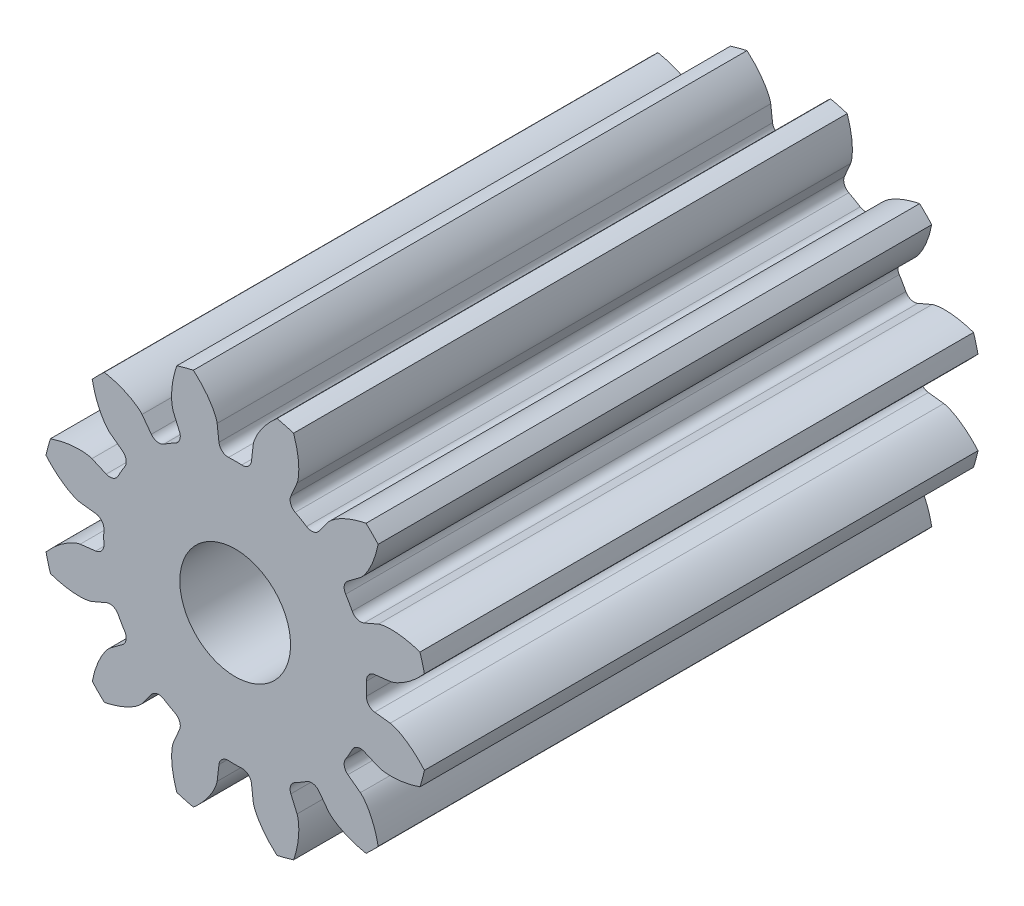
SolidWorks part; units mm, degrees
ref_plane "Front Plane" through (0, 0, 0) normal (0, 0, 1) x (1, 0, 0)
ref_plane "Top Plane" through (0, 0, 0) normal (0, 1, 0) x (1, 0, 0)
ref_plane "Right Plane" through (0, 0, 0) normal (1, 0, 0) x (0, 0, -1)
sketch "Sketch1" plane through (0, 0, 0) normal (0, 0, 1) x (1, 0, 0)
  line L0 (0, 0) -> (0, 4.7625) construction
  line L1 (-1.5306, 5.3196) -> (1.5306, 4.2054) construction
  circle A0 centre (0, 0) radius 3.7703 construction
  circle A1 centre (0, 0) radius 5.5562 construction
  circle A2 centre (0, 0) radius 4.7625 construction
  circle A3 centre (0, 0) radius 4.4753 construction
  point P8 (406.4, 0)
  point P13 (152.4, 0)
  dimension "OD | Outside Diameter" = 11.1125
  dimension "Root Diameter" = 7.5406
  dimension "Gear Pitch Diameter" = 9.525
  dimension "Base Diameter" = 8.9506
  dimension "Pressure Angle" = 20
  dimension "Number of Teeth" = 304.8
  dimension "Gear Pitch | Diametral Pitch" = 812.8
sketch "Sketch2" plane through (0, 0, 0) normal (1, 0, 0) x (0, 0, -1)
  line L0 (-152.4, 0) -> (152.4, 0) construction
  point P2 (-146.8438, 0)
  point P5 (-144.0656, 0)
  point P6 (146.8438, 0)
  dimension "Length" = 304.8
  dimension "D1" = 5.5562
  dimension "D2" = 8.3344
  dimension "D3" = 5.5562
sketch "Sketch3" plane through (0, 0, 0) normal (0, 0, 1) x (1, 0, 0)
  circle A0 centre (0, 0) radius 5.5562
  circle A1 centre (0, 0) radius 5.5562 construction
extrude "Boss-Extrude1" add sketch "Sketch3" against normal up to vertex (152.4 mm away) and the other way up to vertex (152.4 mm away) up to point (0, 0, -152.4) other way up to point (0, 0, 152.4)
sketch "Sketch4" plane through (0, 0, 0) normal (0, 0, 1) x (1, 0, 0)
  line L0 (0, 0) -> (3.745, 0.4364) construction
  line L2 (0, 0) -> (3.745, -0.4364) construction
  line L4 (3.745, 0.4364) -> (4.4452, 0.5179)
  line L5 (4.4452, -0.5179) -> (3.745, -0.4364)
  arc A0 (3.745, 0.4364) -> (3.745, -0.4364) centre (0, 0) cw
  arc A3 (5.4254, 1.1987) -> (5.4254, -1.1987) centre (0, 0) cw
  circle A4 centre (0, 0) radius 5.5562 construction
  spline S0 degree 4 poles (4.4452, 0.5179) (4.447, 0.5182) (4.452, 0.5189) (4.4613, 0.5207) (4.4765, 0.524) (4.4957, 0.5289) (4.5203, 0.5361) (4.5491, 0.5456) (4.5805, 0.5571) (4.6143, 0.5707) (4.6477, 0.5853) (4.6807, 0.6008) (4.7133, 0.6171) (4.7525, 0.6378) (4.799, 0.6639) (4.8525, 0.6964) (4.9122, 0.7355) (4.9721, 0.7778) (5.03, 0.8214) (5.0874, 0.8676) (5.1422, 0.9139) (5.1978, 0.9642) (5.2486, 1.0117) (5.304, 1.0674) (5.3484, 1.113) (5.4053, 1.1756) (5.4385, 1.2134) (5.4767, 1.2584) (5.4934, 1.2789) (5.5037, 1.2914) knots 0 0 0 0 0 0.005377 0.015084 0.028532 0.04661 0.064855 0.092111 0.119476 0.146842 0.174209 0.201575 0.228941 0.256307 0.307035 0.361767 0.4165 0.471232 0.525964 0.580697 0.635429 0.690161 0.744894 0.799626 0.854358 0.909091 0.954545 1 1 1 1 1 construction
  spline S1 degree 4 poles (4.4452, 0.5179) (4.447, 0.5182) (4.452, 0.5189) (4.4613, 0.5207) (4.4765, 0.524) (4.4957, 0.5289) (4.5203, 0.5361) (4.5491, 0.5456) (4.5805, 0.5571) (4.6143, 0.5707) (4.6477, 0.5853) (4.6807, 0.6008) (4.7133, 0.6171) (4.7525, 0.6378) (4.799, 0.6639) (4.8525, 0.6964) (4.9122, 0.7355) (4.9721, 0.7778) (5.03, 0.8214) (5.0874, 0.8676) (5.1422, 0.9139) (5.1978, 0.9642) (5.2486, 1.0117) (5.304, 1.0674) (5.3484, 1.113) (5.393, 1.1621) (5.4145, 1.1862) (5.4254, 1.1987) knots 0 0 0 0 0 0.005377 0.015084 0.028532 0.04661 0.064855 0.092111 0.119476 0.146842 0.174209 0.201575 0.228941 0.256307 0.307035 0.361767 0.4165 0.471232 0.525964 0.580697 0.635429 0.690161 0.744894 0.799626 0.854358 0.909091 0.909091 0.909091 0.909091 0.909091
  spline S2 degree 4 poles (4.4452, -0.5179) (4.447, -0.5182) (4.452, -0.5189) (4.4613, -0.5207) (4.4765, -0.524) (4.4957, -0.5289) (4.5203, -0.5361) (4.5491, -0.5456) (4.5805, -0.5571) (4.6143, -0.5707) (4.6477, -0.5853) (4.6807, -0.6008) (4.7133, -0.6171) (4.7525, -0.6378) (4.799, -0.6639) (4.8525, -0.6964) (4.9122, -0.7355) (4.9721, -0.7778) (5.03, -0.8214) (5.0874, -0.8676) (5.1422, -0.9139) (5.1978, -0.9642) (5.2486, -1.0117) (5.304, -1.0674) (5.3484, -1.113) (5.4053, -1.1756) (5.4385, -1.2134) (5.4767, -1.2584) (5.4934, -1.2789) (5.5037, -1.2914) knots 0 0 0 0 0 0.005377 0.015084 0.028532 0.04661 0.064855 0.092111 0.119476 0.146842 0.174209 0.201575 0.228941 0.256307 0.307035 0.361767 0.4165 0.471232 0.525964 0.580697 0.635429 0.690161 0.744894 0.799626 0.854358 0.909091 0.954545 1 1 1 1 1 construction
  spline S3 degree 4 poles (4.4452, -0.5179) (4.447, -0.5182) (4.452, -0.5189) (4.4613, -0.5207) (4.4765, -0.524) (4.4957, -0.5289) (4.5203, -0.5361) (4.5491, -0.5456) (4.5805, -0.5571) (4.6143, -0.5707) (4.6477, -0.5853) (4.6807, -0.6008) (4.7133, -0.6171) (4.7525, -0.6378) (4.799, -0.6639) (4.8525, -0.6964) (4.9122, -0.7355) (4.9721, -0.7778) (5.03, -0.8214) (5.0874, -0.8676) (5.1422, -0.9139) (5.1978, -0.9642) (5.2486, -1.0117) (5.304, -1.0674) (5.3484, -1.113) (5.393, -1.1621) (5.4145, -1.1862) (5.4254, -1.1987) knots 0 0 0 0 0 0.005377 0.015084 0.028532 0.04661 0.064855 0.092111 0.119476 0.146842 0.174209 0.201575 0.228941 0.256307 0.307035 0.361767 0.4165 0.471232 0.525964 0.580697 0.635429 0.690161 0.744894 0.799626 0.854358 0.909091 0.909091 0.909091 0.909091 0.909091
  dimension "D1" = 7.5406
extrude "Cut-Extrude1" cut sketch "Sketch4" against normal through all both and the other way through all
fillet "Fillet1" radius 0.2663 2 edges at (3.745, -0.4364, 0) (3.745, 0.4364, 0)
pattern_circular "CirPattern1" count 12 over 360 about axis through (0, 0, 152.4) along (0, 0, -1) of "Cut-Extrude1", "Fillet1"
sketch "Sketch6" plane through (0, 0, 152.4) normal (0, 0, 1) x (1, 0, 0)
  circle A0 centre (0, 0) radius 6.35
  dimension "D1" = 12.7
extrude "Cut-Extrude2" cut sketch "Sketch6" against normal blind 288.925
sketch "Sketch7" plane through (0, 0, -152.4) normal (0, 0, -1) x (-1, 0, 0)
  point P0 (0, 0)
hole_wizard "1/8 (0.125) Diameter Hole1" positions "Sketch7" profile "Sketch8" hole size "1/8" standard "ANSI Inch" end condition through all
sketch "Sketch8" plane through (0, 0, -152.4) normal (1, 0, 0) x (0, 1, 0)
  line L0 (0, 0) -> (0, 15.875)
  line L1 (0, 15.875) -> (1.5875, 15.875)
  line L2 (1.5875, 15.875) -> (1.5875, 0)
  line L5 (1.5875, 0) -> (0, 0)
  line L11 (0, -6.35) -> (0, 107.95) construction
  dimension "Thru Hole Dia." = 3.175
  dimension "Thru Hole Depth" = 15.875
equation "\"Root Diameter@Sketch1\"=\"Root Diameter\""
equation "\"OD | Outside Diameter@Sketch1\"=\"Outside Diameter\""
equation "\"D1@CirPattern1\"=\"Number of Teeth\""
equation "\"Diametral Pitch\"=32"
equation "\"Number of Teeth\"=12"
equation "\"Pressure Angle\"=20"
equation "\"Pitch Diameter\"= \"Number of Teeth\" / \"Diametral Pitch\""
equation "\"Base Diameter\"= \"Pitch Diameter\" * cos ( \"Pressure Angle\" )"
equation "\"Outside Diameter\"= ( \"Number of Teeth\" + 2 ) / \"Diametral Pitch\""
equation "\"Dedendum\"= 1.25 / \"Diametral Pitch\""
equation "\"Root Diameter\"= \"Pitch Diameter\" - ( 2 * \"Dedendum\" )"
equation "\"Pitch Angle\"= 360deg / \"Number of Teeth\""
equation "\"Alpha\"= sqr ( \"Pitch Diameter\" ^ 2 - \"Base Diameter\" ^ 2 ) / \"Base Diameter\" * 180 / PI - \"Pressure Angle\""
equation "\"Beta\"= ( \"Pitch Angle\" / 4 - \"Alpha\" )"
equation "\"Phi\"= sqr ( ( \"Outside Diameter\" / 2 ) ^ 2 - ( \"Base Diameter\" / 2 ) ^ 2 ) / ( \"Base Diameter\" / 2 )"
equation "\"Addendum\"= 1 / \"Diametral Pitch\""
equation "\"WorkingDepth\"= 2 / \"Diametral Pitch\""
equation "\"WholeDepth\"= 2.25 / \"Diametral Pitch\""
equation "\"Clearance\"= 0.25 / \"Diametral Pitch\""
equation "\"ToothThickness\"= ( pi * 2 ) / \"Diametral Pitch\""
equation "\"CircularPitch\"= pi / \"Diametral Pitch\""
equation "\"Number of Teeth@Sketch1\"=\"Number of Teeth\""
equation "\"Gear Pitch | Diametral Pitch@Sketch1\"=\"Diametral Pitch\""
equation "\"Pressure Angle@Sketch1\"=\"Pressure Angle\""
equation "\"Gear Pitch Diameter@Sketch1\"=\"Pitch Diameter\""
equation "\"Base Diameter@Sketch1\"=\"Base Diameter\""
equation "\"Fillet\"= \"Clearance\" * cos ( \"Pressure Angle\" ) * tan ( ( 90 + \"Pressure Angle\" ) / 2 )"
equation "\"D1@Fillet1\"=\"Fillet\""
equation "\"D1@Sketch4\"=if( \"Base Diameter\">\"Root Diameter\",\"Root Diameter\",\"Base Diameter\"-.00001)"
equation "\"D1@Sketch2\"=\"OD | Outside Diameter@Sketch1\"*2*0.5*0.5"
equation "\"D2@Sketch2\"=\"D1@Sketch2\"*1.5"
equation "\"D3@Sketch2\"=\"D1@Sketch2\""
